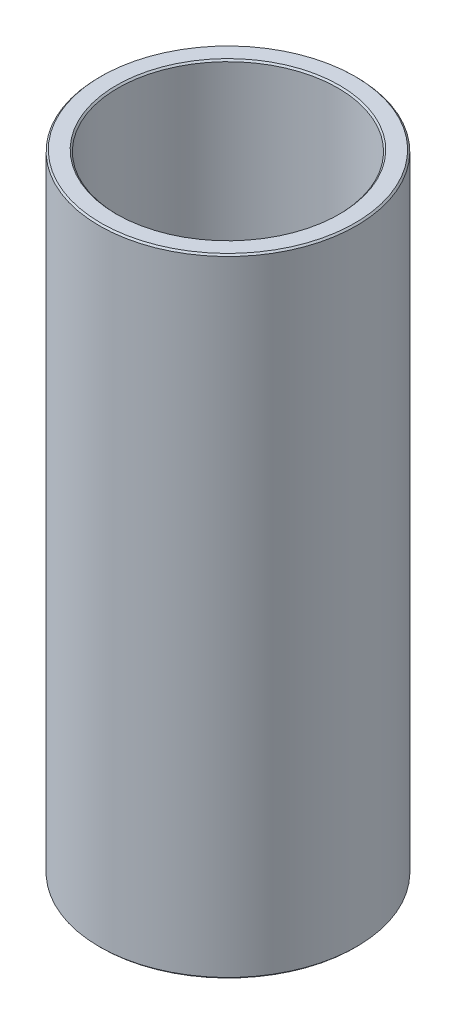
SolidWorks part; units mm, degrees
ref_plane "Front Plane" through (0, 0, 0) normal (0, 0, 1) x (1, 0, 0)
ref_plane "Top Plane" through (0, 0, 0) normal (0, 1, 0) x (1, 0, 0)
ref_plane "Right Plane" through (0, 0, 0) normal (1, 0, 0) x (0, 0, -1)
sketch "Sketch1" plane through (0, 0, 0) normal (0, 1, 0) x (1, 0, 0)
  circle A0 centre (0, 0) radius 27.5
  dimension "SLEEVE_OD" = 55
extrude "Boss-Extrude1" add sketch "Sketch1" along normal blind 134.1795
sketch "Sketch2" plane through (0, 0, 0) normal (0, 1, 0) x (1, 0, 0)
  circle A0 centre (0, 0) radius 23.5292
  dimension "BORE_D" = 47.0583
extrude "Cut-Extrude1" cut sketch "Sketch2" along normal through all
chamfer "Chamfer1" distance 0.3337 angle 45 4 edges at (0, 134.1795, 23.5292) (0, 0, 23.5292) (0, 0, 27.5) (0, 134.1795, 27.5)
